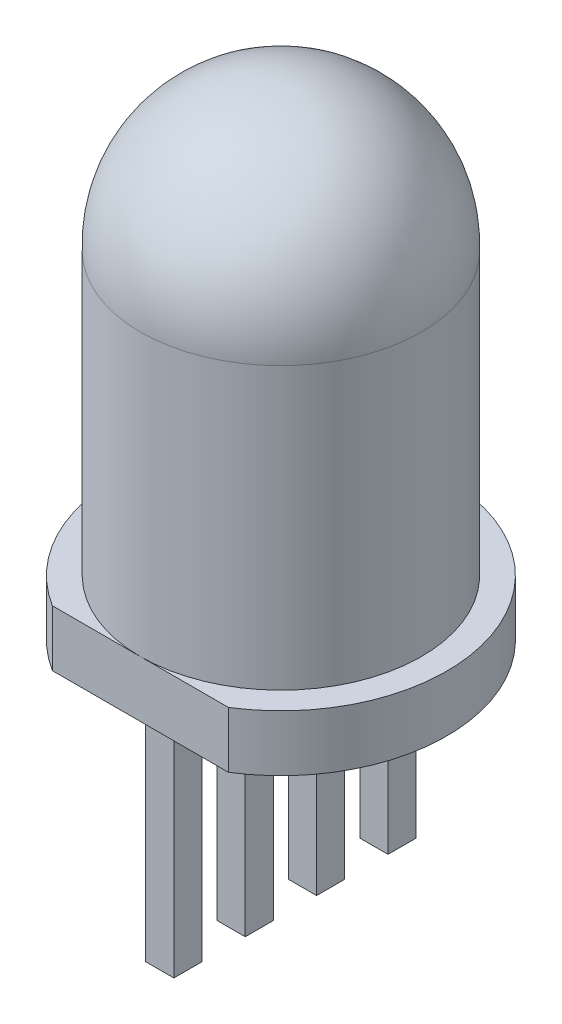
SolidWorks part; units mm, degrees
ref_plane "Front Plane" through (0, 0, 0) normal (0, 0, 1) x (1, 0, 0)
ref_plane "Top Plane" through (0, 0, 0) normal (0, 1, 0) x (1, 0, 0)
ref_plane "Right Plane" through (0, 0, 0) normal (1, 0, 0) x (0, 0, -1)
sketch "Sketch1" plane through (0, 0, 0) normal (0, 1, 0) x (1, 0, 0)
  circle A0 centre (0, 0) radius 2.5
extrude "Boss-Extrude1" add sketch "Sketch1" along normal blind 6
sketch "Sketch2" plane through (0, 0, 0) normal (0, 1, 0) x (1, 0, 0)
  circle A0 centre (0, 0) radius 2.95
extrude "Boss-Extrude2" add sketch "Sketch2" along normal blind 1
dome "Dome1" faces to dome 1 distance 2.6 reverse direction no elliptical dome no face at (0, 6, 2.5) parameters "D1"=2.6
sketch "Sketch3" plane through (0, 0, 0) normal (0, -1, 0) x (1, 0, 0)
  line L1 (-2.1649, 3.016) -> (2.5911, 3.016)
  line L2 (-2.1649, 3.016) -> (-2.1649, 2.5)
  line L3 (-2.1649, 2.5) -> (2.5911, 2.5)
  line L4 (2.5911, 3.016) -> (2.5911, 2.5)
  circle A0 centre (0, 0) radius 2.5 construction
extrude "Cut-Extrude1" cut sketch "Sketch3" against normal up to next
sketch "Sketch4" plane through (0, 0, 0) normal (0, -1, 0) x (1, 0, 0)
  line L0 (0, -0.1654) -> (0, 0.2228) construction
  line L1 (0.25, 2.155) -> (-0.25, 2.155)
  line L2 (0.25, 2.155) -> (0.25, 1.655)
  line L3 (0.25, 1.655) -> (-0.25, 1.655)
  line L4 (-0.25, 2.155) -> (-0.25, 1.655)
  line L5 (0.25, 0.885) -> (-0.25, 0.885)
  line L6 (0.25, 0.885) -> (0.25, 0.385)
  line L7 (0.25, 0.385) -> (-0.25, 0.385)
  line L8 (-0.25, 0.885) -> (-0.25, 0.385)
  line L9 (0.25, -0.385) -> (-0.25, -0.385)
  line L10 (0.25, -0.385) -> (0.25, -0.885)
  line L11 (0.25, -0.885) -> (-0.25, -0.885)
  line L12 (-0.25, -0.385) -> (-0.25, -0.885)
  line L13 (0.25, -1.655) -> (-0.25, -1.655)
  line L14 (0.25, -1.655) -> (0.25, -2.155)
  line L15 (0.25, -2.155) -> (-0.25, -2.155)
  line L16 (-0.25, -1.655) -> (-0.25, -2.155)
  line L17 (0.3119, 0) -> (-0.3875, 0) construction
  dimension "D1" = 0.5
  dimension "D2" = 0.5
  dimension "D3" = 1.27
  dimension "D4" = 1.27
  dimension "D5" = 1.27
extrude "Boss-Extrude3" add sketch "Sketch4" along normal blind 4
